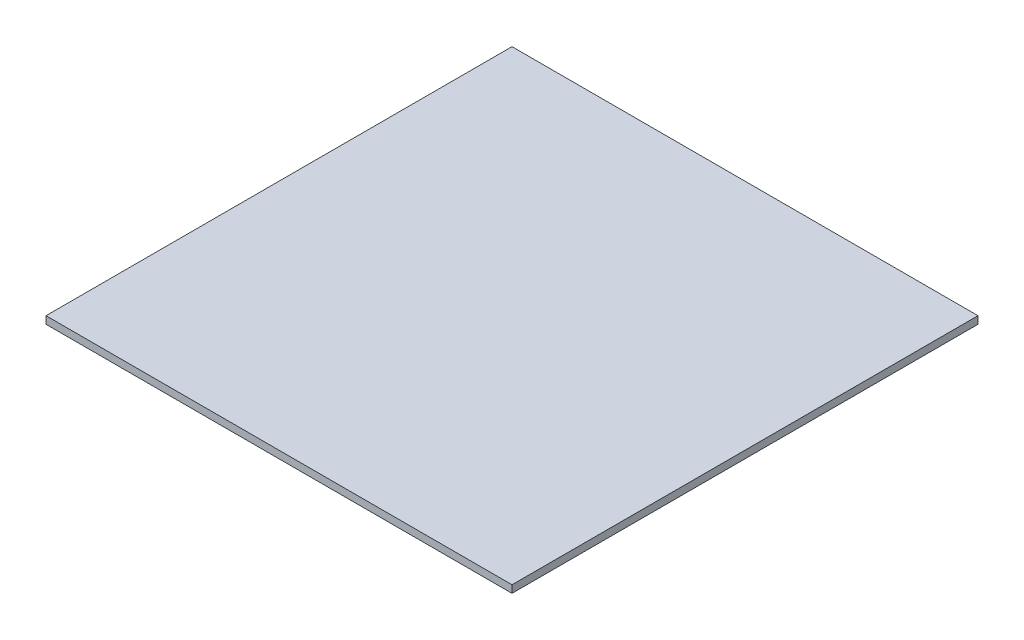
SolidWorks part; units mm, degrees
ref_plane "Спереди" through (0, 0, 0) normal (0, 0, 1) x (1, 0, 0)
ref_plane "Сверху" through (0, 0, 0) normal (0, 1, 0) x (1, 0, 0)
ref_plane "Справа" through (0, 0, 0) normal (1, 0, 0) x (0, 0, -1)
sketch "Эскиз1" plane through (0, 0, 0) normal (0, 1, 0) x (1, 0, 0)
  line L1 (0, 0) -> (250, 0)
  line L2 (0, 0) -> (0, 250)
  line L3 (0, 250) -> (250, 250)
  line L4 (250, 0) -> (250, 250)
  dimension "D1" = 250
  dimension "D2" = 250
extrude "Бобышка-Вытянуть1" add sketch "Эскиз1" along normal blind 4
